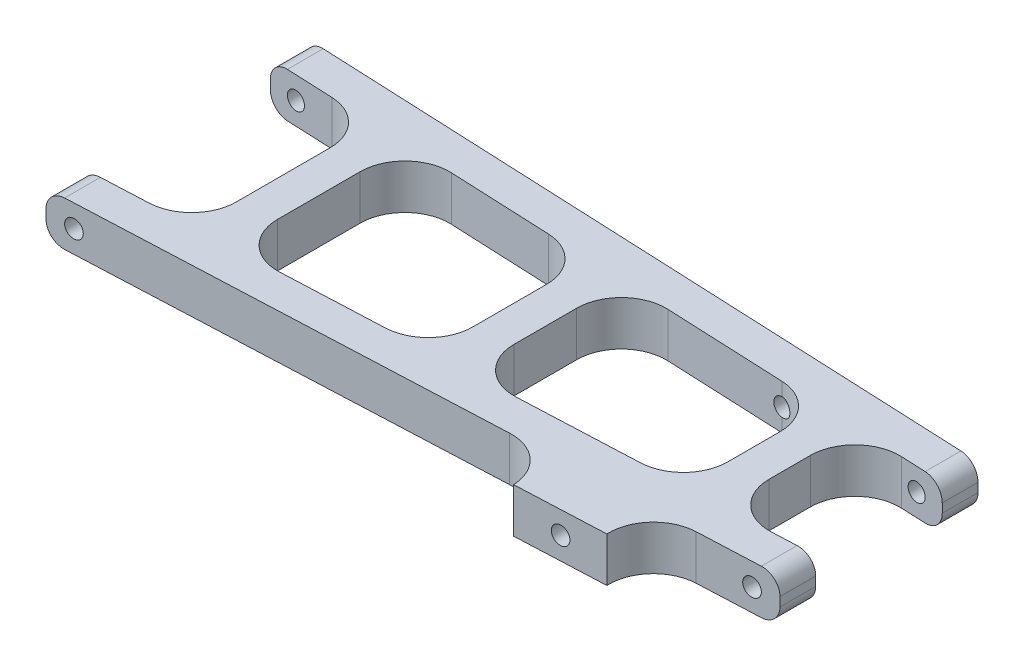
SolidWorks part; units mm, degrees
ref_plane "Front Plane" through (0, 0, 0) normal (0, 0, 1) x (1, 0, 0)
ref_plane "Top Plane" through (0, 0, 0) normal (0, 1, 0) x (1, 0, 0)
ref_plane "Right Plane" through (0, 0, 0) normal (1, 0, 0) x (0, 0, -1)
sketch "Sketch1" plane through (0, 0, 0) normal (0, 1, 0) x (1, 0, 0)
  line L0 (0, -18.5) -> (69.52, -15.4307)
  line L1 (100, -14.0849) -> (100, -9)
  line L2 (100, 14.0849) -> (0, 18.5)
  line L3 (0, 18.5) -> (0, 13.4151)
  line L4 (0, 0) -> (158.8978, 0) construction
  line L5 (0, 13.4151) -> (15.24, 12.7422)
  line L6 (0, -13.4151) -> (0, -18.5)
  line L7 (100, -9) -> (87.3, -9.5607)
  line L8 (87.3, 9.5607) -> (100, 9)
  line L9 (15.24, 12.7422) -> (15.24, -12.7422)
  line L10 (82.22, -9.785) -> (52.54, -11.0954)
  line L11 (20.32, 12.5179) -> (20.32, -12.5179)
  line L12 (50, 16.2925) -> (50, -16.2925) construction
  line L13 (47.46, 11.3197) -> (47.46, -11.3197)
  line L14 (47.46, -11.0954) -> (52.54, -11.0954) construction
  line L15 (52.54, 11.0954) -> (52.54, -11.0954)
  line L16 (52.54, 11.0954) -> (82.22, 9.785)
  line L17 (82.22, 9.785) -> (82.22, -9.785)
  line L18 (47.46, -11.3197) -> (20.32, -12.5179)
  line L19 (87.3, 9.5607) -> (87.3, -9.5607)
  line L20 (100, 9) -> (100, 14.0849)
  line L21 (100, 9) -> (100, -9) construction
  line L22 (0, 13.4151) -> (0, -13.4151) construction
  line L23 (20.32, 12.5179) -> (47.46, 11.3197)
  line L24 (15.24, -12.7422) -> (0, -13.4151)
  line L25 (82.22, -14.8699) -> (82.5001, -21.2138)
  line L26 (82.5001, -21.2138) -> (69.8001, -21.7745)
  line L27 (69.8001, -21.7745) -> (69.52, -15.4307)
  line L28 (82.22, -14.8699) -> (100, -14.0849)
  point P28 (50, -11.0954)
  dimension "D2" = 18
  dimension "D3" = 100
  dimension "D5" = 5.08
  dimension "D6" = 5.08
  dimension "D4" = 5.08
  dimension "D7" = 5.08
  dimension "D8" = 5.08
  dimension "D9" = 12.7
  dimension "D10" = 15.24
  dimension "D11" = 6.35
  dimension "D12" = 12.7
  dimension "D13" = 17.78
  dimension "D14" = 26.8301
extrude "Arm" add sketch "Sketch1" along normal blind 6.35
sketch "Sketch2" plane through (0, 0, 0) normal (0, 0, 1) x (1, 0, 0)
  line L0 (76.2, 6.35) -> (76.2, 0) construction
  line L1 (0, 6.35) -> (69.52, 6.35) construction
  line L2 (0, 0) -> (69.52, 0) construction
  line L3 (0, 6.35) -> (0, 0) construction
  circle A0 centre (76.2, 3.175) radius 1.27
  dimension "D1" = 2.54
  dimension "D2" = 76.2
extrude "Cut-Extrude1" cut sketch "Sketch2" against normal through all and the other way through all
sketch "Sketch3" plane through (0, 0, 0) normal (0, 0, 1) x (1, 0, 0)
  line L0 (96.19, 6.35) -> (96.19, 0) construction
  line L1 (100, 6.35) -> (0, 6.35) construction
  line L2 (100, 0) -> (0, 0) construction
  line L3 (100, 6.35) -> (100, 0) construction
  line L4 (3.81, 6.35) -> (3.81, 0) construction
  line L5 (0, 6.35) -> (0, 0) construction
  circle A0 centre (96.19, 3.175) radius 1.27
  circle A1 centre (3.81, 3.175) radius 1.27
  dimension "D1" = 2.54
  dimension "D4" = 2.54
  dimension "D2" = 3.81
  dimension "D3" = 3.81
extrude "Cut-Extrude2" cut sketch "Sketch3" against normal through all and the other way through all
fillet "Fillet1" radius 2.54 8 edges at (0, 0, -15.9575) (0, 6.35, -15.9575) (100, 0, 11.5425) (100, 6.35, 11.5425) (100, 0, -11.5425) (100, 6.35, -11.5425) (0, 0, 15.9575) (0, 6.35, 15.9575)
mirror "Mirror2" [suppressed] about plane through (0, 0, 0) normal (0, 0, 1)
fillet "Fillet2" radius 6.35 12 edges at (15.24, 3.175, 12.7422) (15.24, 3.175, -12.7422) (87.3, 3.175, 9.5607) (47.46, 3.175, 11.3197) (52.54, 3.175, 11.0954) (20.32, 3.175, 12.5179) (20.32, 3.175, -12.5179) (87.3, 3.175, -9.5607) (82.22, 3.175, 9.785) (52.54, 3.175, -11.0954) (82.22, 3.175, -9.785) (47.46, 3.175, -11.3197)
fillet "Fillet3" radius 6.35 2 edges at (69.52, 3.175, 15.4307) (82.22, 3.175, 14.8699)
